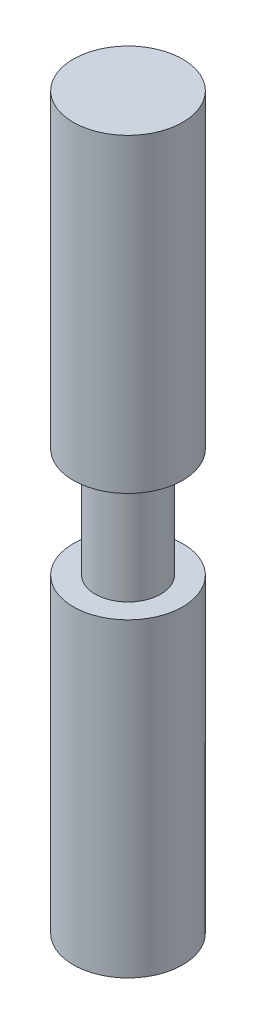
SolidWorks part; units mm, degrees
ref_plane "Front Plane" through (0, 0, 0) normal (0, 0, 1) x (1, 0, 0)
ref_plane "Top Plane" through (0, 0, 0) normal (0, 1, 0) x (1, 0, 0)
ref_plane "Right Plane" through (0, 0, 0) normal (1, 0, 0) x (0, 0, -1)
sketch "Sketch1" plane through (0, 0, 0) normal (0, 1, 0) x (1, 0, 0)
  circle A0 centre (0, 0) radius 5.715
  dimension "D1" = 11.43
extrude "Boss-Extrude1" add sketch "Sketch1" along normal blind 19.05
sketch "Sketch2" plane through (0, 19.05, 0) normal (0, 1, 0) x (1, 0, 0)
  circle A0 centre (0, 0) radius 9.525
extrude "Boss-Extrude2" add sketch "Sketch2" along normal blind 53.975
sketch "Sketch3" plane through (0, 0, 0) normal (0, -1, 0) x (1, 0, 0)
  circle A0 centre (0, 0) radius 9.525
extrude "Boss-Extrude3" add sketch "Sketch3" along normal blind 53.975
